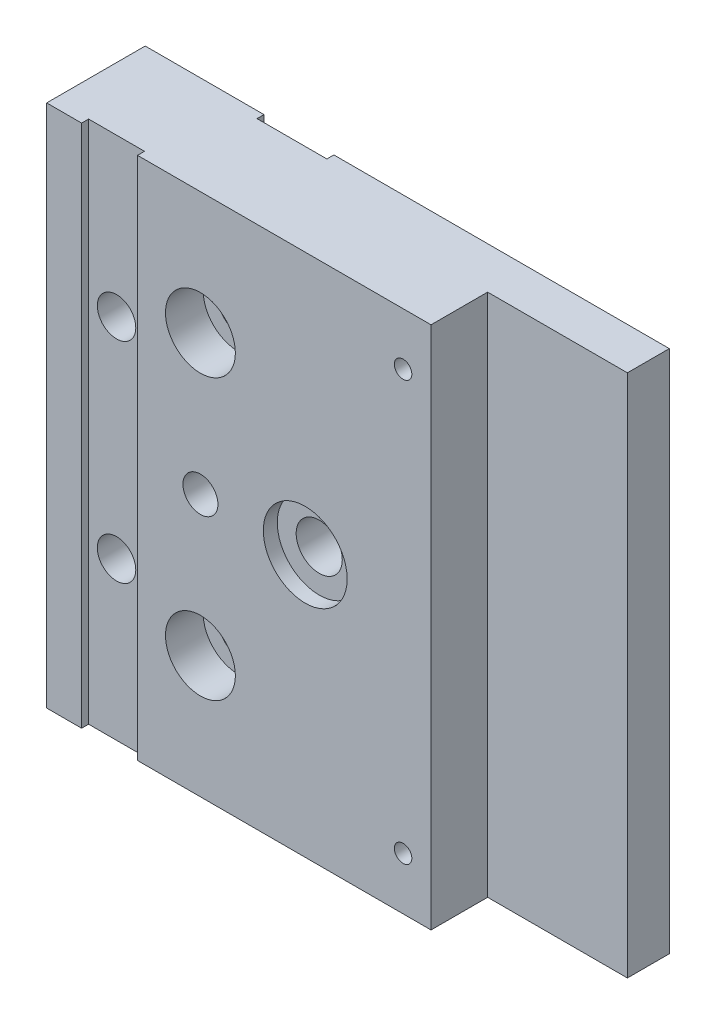
SolidWorks part; units mm, degrees
ref_plane "前视基准面" through (0, 0, 0) normal (0, 0, 1) x (1, 0, 0)
ref_plane "上视基准面" through (0, 0, 0) normal (0, 1, 0) x (1, 0, 0)
ref_plane "右视基准面" through (0, 0, 0) normal (1, 0, 0) x (0, 0, -1)
sketch "草图1" plane through (0, 0, 0) normal (0, 0, 1) x (1, 0, 0)
  line L1 (0, 0) -> (20, 0)
  line L2 (0, 0) -> (0, 75)
  line L3 (0, 75) -> (20, 75)
  line L4 (20, 0) -> (20, 75)
  dimension "D1" = 20
  dimension "D2" = 75
extrude "凸台-拉伸1" add sketch "草图1" along normal blind 6
sketch "草图2" plane through (0, 0, 0) normal (-1, 0, 0) x (0, 0, 1)
  line L1 (0, 75) -> (6, 75)
  line L2 (0, 75) -> (0, 0)
  line L3 (0, 0) -> (6, 0)
  line L4 (6, 75) -> (6, 0)
extrude "凸台-拉伸2" add sketch "草图2" along normal blind 20
sketch "草图3" plane through (0, 0, 6) normal (0, 0, 1) x (1, 0, 0)
  line L0 (-20, 0) -> (20, 0) construction
  line L1 (-20, 75) -> (0, 75)
  line L2 (-20, 75) -> (-20, 0)
  line L3 (-20, 0) -> (0, 0)
  line L4 (0, 75) -> (0, 0)
  dimension "D1" = 20
extrude "凸台-拉伸3" add sketch "草图3" along normal blind 8.1
sketch "草图4" plane through (-20, 0, 0) normal (-1, 0, 0) x (0, 0, 1)
  line L1 (14.1, 0) -> (0, 0)
  line L2 (14.1, 0) -> (14.1, 75)
  line L3 (14.1, 75) -> (0, 75)
  line L4 (0, 0) -> (0, 75)
extrude "凸台-拉伸4" add sketch "草图4" along normal blind 35
hole_wizard "M6 六角凹头螺钉的柱形沉头孔1" positions "草图7" profile "草图8" counterbore size "M6" standard "ISO" end condition through all
sketch "草图7" plane through (0, 0, 0) normal (0, 0, -1) x (-1, 0, 0)
  line L0 (55, 37.5) -> (-1.4171, 37.5) construction
  line L1 (55, 75) -> (55, 0) construction
  point P0 (18, 37.5)
  dimension "D1" = 37
sketch "草图8" plane through (-18, 37.5, 0) normal (1, 0, 0) x (0, 1, 0)
  line L0 (0, 0) -> (0, 14.1)
  line L1 (0, 14.1) -> (3.3, 14.1)
  line L3 (3.3, 14.1) -> (3.3, 6.4)
  line L4 (3.3, 6.4) -> (5.5, 6.4)
  line L5 (5.5, 6.4) -> (5.5, 0)
  line L7 (5.5, 0) -> (0, 0)
  line L11 (0, -6.35) -> (0, 107.95) construction
  dimension "通孔孔直径" = 6.6
  dimension "通孔孔深度" = 14.1
  dimension "柱形沉头孔直径" = 11
  dimension "柱形沉头孔深度" = 6.4
sketch "草图9" plane through (0, 0, 14.1) normal (0, 0, 1) x (1, 0, 0)
  circle A0 centre (-18, 37.5) radius 6
  dimension "D1" = 12
extrude "切除-拉伸1" cut sketch "草图9" against normal blind 2
hole_wizard "M3 螺纹孔1" positions "草图10" profile "草图11" tap size "M3" standard "ISO"
sketch "草图10" plane through (0, 0, 14.1) normal (0, 0, 1) x (1, 0, 0)
  point P0 (-4, 7.5)
  point P3 (-4, 67.5)
sketch "草图11" plane through (-4, 7.5, 14.1) normal (1, 0, 0) x (0, -1, 0)
  line L0 (0, 0) -> (0, 10.8511)
  line L1 (0, 10.8511) -> (1.25, 10.1)
  line L2 (1.25, 10.1) -> (1.25, 0)
  line L5 (1.25, 0) -> (0, 0)
  line L10 (0, 10.8511) -> (-1.25, 10.1) construction
  line L11 (0, -6.35) -> (0, 107.95) construction
  dimension "螺纹孔钻头直径" = 2.5
  dimension "螺纹孔钻头深度" = 10.1
  dimension "导头角度" = 118
cosmetic thread "孔螺蚊线3" parameters "D1"=6, "D2"=3
cosmetic thread "孔螺蚊线4" parameters "D1"=6, "D2"=3
sketch "草图15" plane through (0, 0, 14.1) normal (0, 0, 1) x (1, 0, 0)
  line L0 (-55, 0) -> (0, 0) construction
  line L1 (-42, 0) -> (-50, 0)
  line L2 (-42, 0) -> (-42, 75)
  line L3 (-42, 75) -> (-50, 75)
  line L4 (-50, 0) -> (-50, 75)
  line L5 (0, 75) -> (-55, 75) construction
  line L6 (-55, 0) -> (-55, 75) construction
  dimension "D1" = 5
  dimension "D2" = 8
extrude "切除-拉伸3" cut sketch "草图15" against normal blind 1
hole_wizard "M5 六角凹头螺钉的柱形沉头孔1" positions "草图16" profile "草图17" counterbore size "M5" standard "ISO" end condition through all
sketch "草图16" plane through (0, 0, 0) normal (0, 0, -1) x (-1, 0, 0)
  line L0 (55, 37.5) -> (34.1733, 37.5) construction
  line L1 (55, 75) -> (55, 0) construction
  point P0 (46, 52.5)
  point P2 (46, 22.5)
  dimension "D1" = 9
  dimension "D2" = 30
sketch "草图17" plane through (-46, 52.5, 0) normal (1, 0, 0) x (0, 1, 0)
  line L0 (0, 0) -> (0, 14.1)
  line L1 (0, 14.1) -> (2.75, 14.1)
  line L3 (2.75, 14.1) -> (2.75, 5.4)
  line L4 (2.75, 5.4) -> (5, 5.4)
  line L5 (5, 5.4) -> (5, 0)
  line L7 (5, 0) -> (0, 0)
  line L11 (0, -6.35) -> (0, 107.95) construction
  dimension "通孔孔直径" = 5.5
  dimension "通孔孔深度" = 14.1
  dimension "柱形沉头孔直径" = 10
  dimension "柱形沉头孔深度" = 5.4
hole_wizard "M6 螺纹孔1" positions "草图20" profile "草图21" tap size "M6" standard "ISO"
sketch "草图20" plane through (0, 0, 14.1) normal (0, 0, 1) x (1, 0, 0)
  line L0 (-42, 37.5) -> (0, 37.5) construction
  line L1 (-42, 0) -> (-42, 75) construction
  line L2 (0, 0) -> (0, 75) construction
  line L4 (-55, 0) -> (-55, 75) construction
  point P0 (-33, 37.5)
  dimension "D1" = 22
sketch "草图21" plane through (-33, 37.5, 14.1) normal (1, 0, 0) x (0, -1, 0)
  line L0 (0, 0) -> (0, 16.5022)
  line L1 (0, 16.5022) -> (2.5, 15)
  line L2 (2.5, 15) -> (2.5, 0)
  line L5 (2.5, 0) -> (0, 0)
  line L10 (0, 16.5022) -> (-2.5, 15) construction
  line L11 (0, -6.35) -> (0, 107.95) construction
  dimension "螺纹孔钻头直径" = 5
  dimension "螺纹孔钻头深度" = 15
  dimension "导头角度" = 118
cosmetic thread "孔螺蚊线5" parameters "D1"=12, "D2"=6
hole_wizard "M5 六角凹头螺钉的柱形沉头孔2" positions "草图22" profile "草图23" counterbore size "M5" standard "ISO" end condition through all
sketch "草图22" plane through (0, 0, 14.1) normal (0, 0, 1) x (1, 0, 0)
  line L0 (-42, 37.5) -> (10.2455, 37.5) construction
  line L1 (-42, 0) -> (-42, 75) construction
  line L3 (-55, 0) -> (-55, 75) construction
  point P0 (-33, 57.5)
  point P8 (-33, 17.5)
  dimension "D1" = 40
  dimension "D2" = 22
sketch "草图23" plane through (-33, 57.5, 14.1) normal (1, 0, 0) x (0, -1, 0)
  line L0 (0, 0) -> (0, 14.1)
  line L1 (0, 14.1) -> (2.75, 14.1)
  line L3 (2.75, 14.1) -> (2.75, 5.4)
  line L4 (2.75, 5.4) -> (5, 5.4)
  line L5 (5, 5.4) -> (5, 0)
  line L7 (5, 0) -> (0, 0)
  line L11 (0, -6.35) -> (0, 107.95) construction
  dimension "通孔孔直径" = 5.5
  dimension "通孔孔深度" = 14.1
  dimension "柱形沉头孔直径" = 10
  dimension "柱形沉头孔深度" = 5.4
sketch "草图24" plane through (0, 0, 0) normal (0, 0, -1) x (-1, 0, 0)
  line L0 (33, 57.5) -> (33, 17.5) construction
  line L1 (-20, 75) -> (55, 75) construction
  line L2 (28, 75) -> (38, 75)
  line L3 (28, 75) -> (28, 0)
  line L4 (28, 0) -> (38, 0)
  line L5 (38, 75) -> (38, 0)
  line L6 (55, 0) -> (-20, 0) construction
  dimension "D1" = 10
extrude "切除-拉伸4" cut sketch "草图24" against normal blind 1
